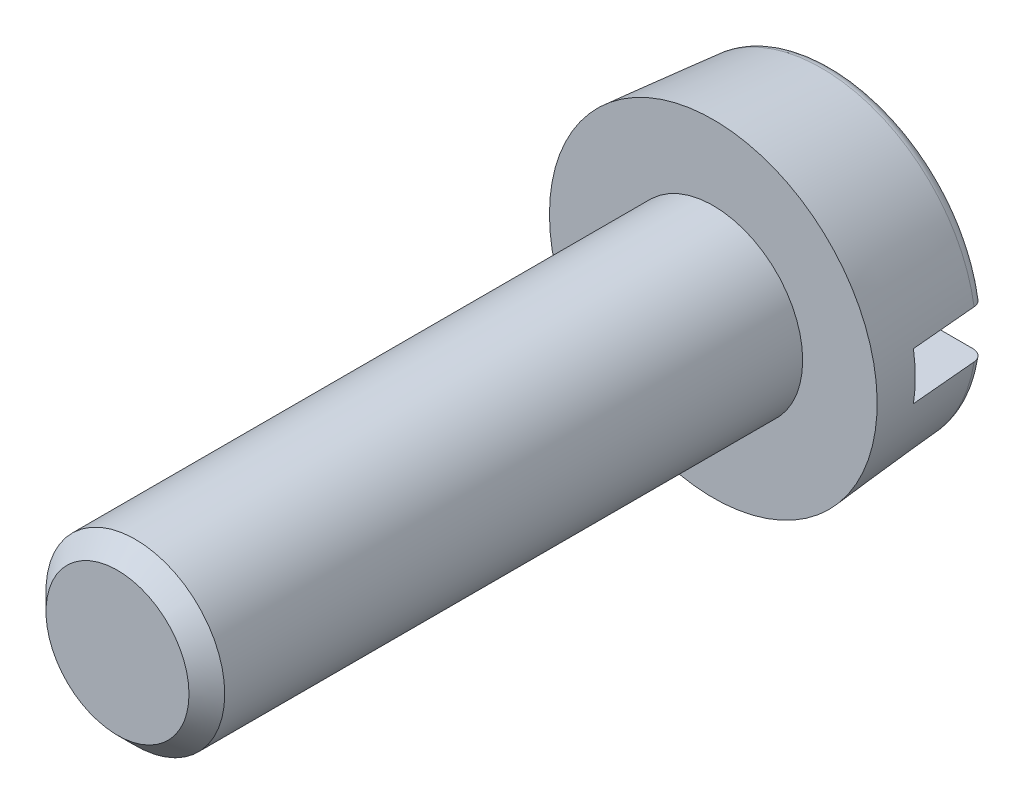
SolidWorks part; units mm, degrees
material "Acier allié"
ref_plane "Plan1" through (0, 0, 0) normal (0, 0, 1) x (1, 0, 0)
ref_plane "Plan2" through (0, 0, 0) normal (0, 1, 0) x (1, 0, 0)
ref_plane "Plan3" through (0, 0, 0) normal (1, 0, 0) x (0, 0, -1)
ref_axis "Z Axis" through (0, 0, -50) along (0, 0, 1)
sketch "Esquisse1" plane through (0, 0, 0) normal (0, 1, 0) x (1, 0, 0)
  line L0 (0, 0) -> (0, 2) construction
  line L1 (0, 0) -> (2.75, 0)
  line L2 (0, 0) -> (0, 2)
  line L3 (0, 2) -> (2.3918, 2)
  line L5 (2.75, 0) -> (2.591, 1.8174)
  arc A0 (2.3918, 2) -> (2.591, 1.8174) centre (2.3918, 1.8) cw
  dimension "D3" = 0.2
  dimension "D1" = 2.75
  dimension "D2" = 2
  dimension "D4" = 5
revolve "Base-Révolution" add sketch "Esquisse1" angle 360 about L0 reverse direction yes
sketch "Esquisse2" plane through (0, 0, -2) normal (0, 0, 1) x (1, 0, 0)
  line L1 (-2.75, 0.4) -> (2.75, 0.4)
  line L2 (-2.75, 0.4) -> (-2.75, -0.4)
  line L3 (-2.75, -0.4) -> (2.75, -0.4)
  line L4 (2.75, 0.4) -> (2.75, -0.4)
  circle A0 centre (0, 0) radius 2.75 construction
  dimension "D1" = 0.4
extrude "Enlev. mat.-Extru.1" cut sketch "Esquisse2" along normal blind 1.3
sketch "Esquisse3" plane through (0, 0, 0) normal (0, 1, 0) x (1, 0, 0)
  line L1 (0, 0) -> (0, -10) construction
  line L2 (0, 0) -> (1.5, 0)
  line L3 (0, 0) -> (0, -10)
  line L4 (0, -10) -> (1.5, -10)
  line L6 (1.5, 0) -> (1.5, -10)
  dimension "D1" = 10
  dimension "D2" = 1.5
revolve "Boss.-Révol.1" add sketch "Esquisse3"
cosmetic thread "Représentation de filetage1" [suppressed]
chamfer "Chanfrein1" distance 0.3 angle 45 1 edges at (1.5, 0, 10)
sketch "Esquisse4" plane through (0, 0, 0) normal (0, 1, 0) x (1, 0, 0)
  line L0 (1.195, -10.0305) -> (1.195, -9.9695)
  line L2 (1.195, -9.9695) -> (1.5305, -9.7758)
  line L3 (1.195, -10.0305) -> (1.5305, -10.2242)
  line L4 (1.5305, -9.7758) -> (1.5305, -10.2242)
  line L6 (1.5, 0) -> (1.5, -10) construction
  line L7 (0, -10) -> (1.5, -10) construction
  point P4 (1.5, -10)
  dimension "D2" = 0.0305
  dimension "D3" = 0.0305
  dimension "D4" = 0.3355
  dimension "D5" = 60
  dimension "D1" = 0.305
  dimension "D6" = 60
sketch "Esquisse5" plane through (0, 0, 10) normal (0, 0, 1) x (1, 0, 0)
  circle A0 centre (0, 0) radius 1.5 construction
  circle A1 centre (0, 0) radius 1.5
curve "Hélice1" pitch 0.5 height 9.8 turns 19.6
sweep "Enlèvement de matière-Balayage1" [suppressed] cut profiles "Esquisse4" path "Hélice1"
equation "\"D3@Esquisse1\"=\"D2@Esquisse1\"/10"
equation "\"D1@Chanfrein1\"=\"D2@Esquisse3\"*0.2"
equation "\"D3@Esquisse4\"=0.1*\"D1@Esquisse4\""
equation "\"D4@Esquisse4\"=1.1*\"D1@Esquisse4\""
equation "\"D2@Esquisse4\"=0.1*\"D1@Esquisse4\""
equation "\"D1@Esquisse4\"=0.61*\"D4@Hélice1\""
equation "\"D1@Représentation de filetage1\"=\"D3@Hélice1\""
equation "\"D2@Représentation de filetage1\"=\"D2@Esquisse3\"*1.6"
